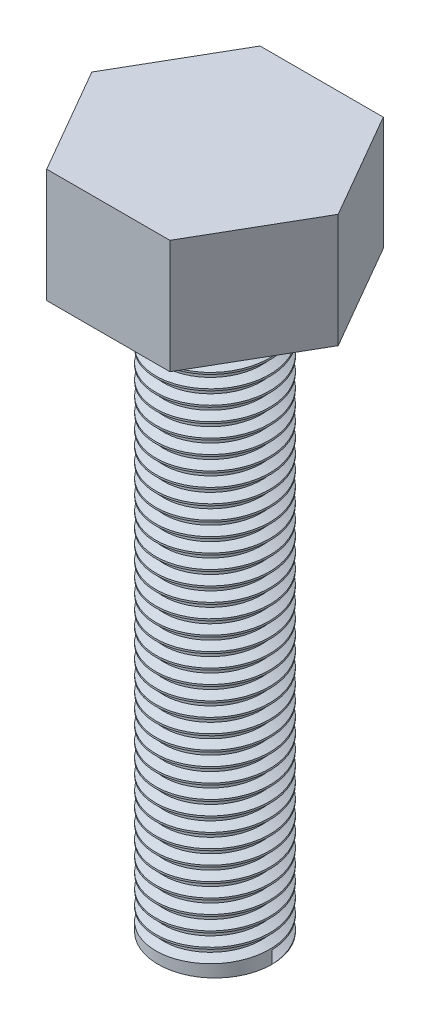
SolidWorks part; units mm, degrees
material "AISI 1020"
ref_plane "Front Plane" through (0, 0, 0) normal (0, 0, 1) x (1, 0, 0)
ref_plane "Top Plane" through (0, 0, 0) normal (0, 1, 0) x (1, 0, 0)
ref_plane "Right Plane" through (0, 0, 0) normal (1, 0, 0) x (0, 0, -1)
sketch "Sketch1" plane through (0, 0, 0) normal (0, 1, 0) x (1, 0, 0)
  circle A0 centre (0, 0) radius 4
  dimension "D1" = 8
extrude "Boss-Extrude1" add sketch "Sketch1" against normal blind 40
sketch "Sketch2" plane through (0, 0, 0) normal (0, 1, 0) x (1, 0, 0)
  line L1 (-8.6603, 0) -> (-4.3301, -7.5)
  line L2 (-4.3301, -7.5) -> (4.3301, -7.5)
  line L3 (4.3301, -7.5) -> (8.6603, 0)
  line L4 (8.6603, 0) -> (4.3301, 7.5)
  line L5 (4.3301, 7.5) -> (-4.3301, 7.5)
  line L6 (-4.3301, 7.5) -> (-8.6603, 0)
  circle A0 centre (0, 0) radius 7.5 construction
  dimension "D1" = 15
extrude "Boss-Extrude2" add sketch "Sketch2" along normal blind 8 contours L3 L4 L5 L6 L1 L2
thread "Thread1" pitch 1 profile "Thread Profile1" start angle 0, offset 0, length 40, pitch 1, diameter 8
ref_plane "Plane1" through (4, -40, 0) normal (0, 0, 1) x (1, 0, 0)
sketch "Thread Profile1" plane through (4, -40, 0) normal (0, 0, 1) x (1, 0, 0)
  line L0 (0, 0) -> (0, 1) construction
  line L11 (0, 0) -> (0, 0.875)
  line L12 (0, 0.875) -> (-0.5413, 0.5625)
  line L13 (-0.5413, 0.5625) -> (-0.5413, 0.3125)
  line L15 (-0.5413, 0.3125) -> (0, 0)
  line L17 (-0.5413, 0.4375) -> (0, 0.4375) construction
  point P2 (0, 0)
  dimension "Pitch" = 1
  dimension "Profile_Angle" = 60
  dimension "Profile_Land" = 0.25
  dimension "Profile_Height" = 0.5413
